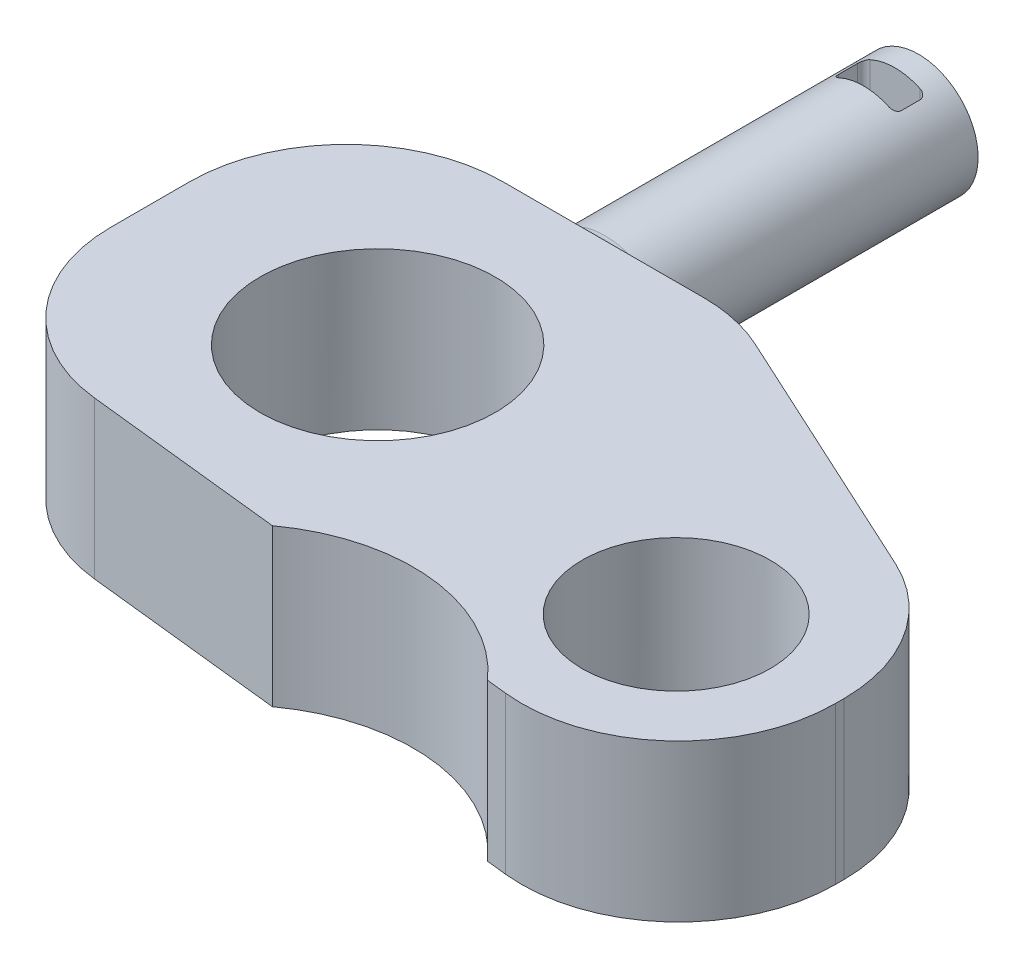
SolidWorks part; units mm, degrees
ref_plane "Front" through (0, 0, 0) normal (0, 0, 1) x (1, 0, 0)
ref_plane "Top" through (0, 0, 0) normal (0, 1, 0) x (1, 0, 0)
ref_plane "Right" through (0, 0, 0) normal (1, 0, 0) x (0, 0, -1)
sketch "Sketch1" plane through (0, 0, 0) normal (0, 0, 1) x (1, 0, 0)
  circle A0 centre (0, 0) radius 5
  dimension "D1" = 10
extrude "Boss-Extrude1" add sketch "Sketch1" along normal blind 20
sketch "Sketch2" plane through (0, 0, 0) normal (0, 0, -1) x (-1, 0, 0)
  circle A0 centre (0, 0) radius 3.98
  circle A1 centre (0, 0) radius 5 construction
  circle A2 centre (0, 0) radius 5
  dimension "D1" = 7.96
extrude "Cut-Extrude2" cut sketch "Sketch2" against normal blind 8 contours A0 | A2
sketch "Sketch8" plane through (0, 0, 20) normal (0, 0, 1) x (1, 0, 0)
  circle A0 centre (0, 0) radius 5
  dimension "D1" = 10
extrude "Boss-Extrude2" add sketch "Sketch8" along normal blind 20
sketch "Sketch9" plane through (0, 0, 40) normal (0, 0, 1) x (1, 0, 0)
  line L1 (0, 5) -> (35, 5)
  line L3 (0, -5) -> (35, -5)
  line L4 (35, 5) -> (35, -5)
  circle A1 centre (0, 0) radius 5 construction
  arc A2 (0, -5) -> (0, 5) centre (0, 0) ccw
  dimension "D1" = 35
  dimension "D2" = 5
  dimension "D3" = 10
extrude "Boss-Extrude3" add sketch "Sketch9" against normal blind 31.5
sketch "Sketch10" plane through (0, 0, 40) normal (0, 0, 1) x (1, 0, 0)
  line L5 (0, 5) -> (-15, 5)
  line L7 (0, -5) -> (-15, -5)
  line L8 (-15, 5) -> (-15, -5)
  arc A0 (0, 5) -> (0, -5) centre (0, 0) ccw construction
  arc A1 (0, 5) -> (0, -5) centre (0, 0) ccw
  dimension "D1" = 15
extrude "Boss-Extrude4" add sketch "Sketch10" against normal blind 31.5
sketch "Sketch12" plane through (0, 5, 0) normal (0, 1, 0) x (1, 0, 0)
  line L0 (0, -8.5) -> (-15, -8.5) construction
  line L3 (0, -21.5) -> (73.8631, -37.7534) construction
  line L4 (0, -21.5) -> (73.9968, -21.5) construction
  circle A0 centre (0, -21.5) radius 7.5
  circle A3 centre (24.4159, -26.8726) radius 6
  dimension "D1" = 15
  dimension "D3" = 12.41
  dimension "D4" = 12
  dimension "D2" = 13
  dimension "D5" = 25
extrude "Cut-Extrude3" cut sketch "Sketch12" against normal blind 31.5
sketch "Sketch14" plane through (0, 5, 0) normal (0, 1, 0) x (1, 0, 0)
  line L1 (35, -8.5) -> (0, -8.5) construction
  line L2 (35, -8.5) -> (35, -40) construction
  line L4 (-15, -8.5) -> (-15, -40) construction
  line L6 (-15, -40) -> (35, -40)
  line L7 (35, -40) -> (35, -37.3683)
  line L8 (34.4159, -37.8726) -> (-15, -32.5)
  line L9 (-15, -32.5) -> (-15, -40)
  line L10 (34.4159, -19.7562) -> (34.4159, -37.8726)
  line L11 (-15, -40) -> (35, -40)
  line L12 (35, -40) -> (35, -8.5)
  line L13 (35, -8.5) -> (0, -8.5)
  line L14 (0, -8.5) -> (-15, -8.5)
  line L15 (-15, -8.5) -> (-15, -40)
  line L18 (35, -8.5) -> (10, -8.5)
  line L22 (35, -37.3683) -> (35, -8.5)
  line L23 (10, -8.5) -> (34.4159, -19.7562)
  circle A0 centre (0, -21.5) radius 7.5 construction
  dimension "D2" = 10
  dimension "D3" = 11
  dimension "D4" = 7.1164
  dimension "D6" = 10
  dimension "D7" = 11
  dimension "D1" = 0
extrude "Cut-Extrude4" cut sketch "Sketch14" against normal through all
fillet "Fillet1" radius 10 5 edges at (-15, 0, 8.5) (-15, 0, 32.5) (34.4159, 0, 37.8726) (34.4159, 0, 19.7562) (10, 0, 8.5)
sketch "Sketch15" plane through (0, 5, 0) normal (0, 1, 0) x (1, 0, 0)
  line L0 (0, -21.5) -> (57.2418, -34.0932)
  line L1 (0, -21.5) -> (51.5086, -21.5)
  dimension "D1" = 12.407
sketch "Sketch17" plane through (0, 0, 0) normal (0, 0, -1) x (-1, 0, 0)
  circle A1 centre (0, 0) radius 3.98
  circle A2 centre (0, 0) radius 3.98
  dimension "D1" = 0
extrude "Boss-Extrude5" add sketch "Sketch17" along normal blind 13
sketch "Sketch18" plane through (0, 5, 0) normal (0, 1, 0) x (1, 0, 0)
  line L0 (-3.98, 8) -> (3.98, 8) construction
  line L1 (-3.98, 13) -> (-3.98, -8) construction
  line L2 (3.98, -8) -> (3.98, 13) construction
  line L3 (3.98, 13) -> (-3.98, 13) construction
  line L4 (0, 8) -> (0, 13) construction
  line L5 (-1.6, 11.5) -> (1.6, 11.5)
  line L6 (-2, 11.1) -> (-2, 9.9)
  line L7 (-1.6, 9.5) -> (1.6, 9.5)
  line L8 (2, 11.1) -> (2, 9.9)
  line L9 (-2, 10.5) -> (2, 10.5) construction
  arc A0 (1.6, 11.5) -> (2, 11.1) centre (1.6, 11.1) cw
  arc A1 (1.6, 9.5) -> (2, 9.9) centre (1.6, 9.9) ccw
  arc A2 (-2, 9.9) -> (-1.6, 9.5) centre (-1.6, 9.9) ccw
  arc A3 (-1.6, 11.5) -> (-2, 11.1) centre (-1.6, 11.1) ccw
  point P14 (0, 10.5)
  point P17 (0, 10.5)
  point P22 (2, 11.5)
  point P25 (2, 9.5)
  point P30 (-2, 11.5)
  dimension "D4" = 0.4
  dimension "D1" = 5
  dimension "D2" = 2
  dimension "D3" = 4
extrude "Cut-Extrude5" cut sketch "Sketch18" against normal through all
sketch "Sketch19" plane through (0, 0, 8) normal (0, 0, -1) x (-1, 0, 0)
  circle A0 centre (0, 0) radius 5 construction
  circle A1 centre (0, 0) radius 3.98
  circle A2 centre (0, 0) radius 3.98
  circle A3 centre (0, 0) radius 5
  dimension "D1" = 0
extrude "Cut-Extrude6" cut sketch "Sketch19" against normal up to surface (0.5 mm away) up to face at (5.1529, 0, 8.5)
sketch "Sketch20" plane through (0, 0, -13) normal (0, 0, -1) x (-1, 0, 0)
  circle A0 centre (0, 0) radius 3.8
  circle A1 centre (0, 0) radius 3.98 construction
  circle A2 centre (0, 0) radius 3.98
  dimension "D1" = 7.6
extrude "Cut-Extrude7" cut sketch "Sketch20" against normal up to surface (21.5 mm away) up to face at (1.4029, 0, 8.5)
fillet "Fillet2" radius 1.5 1 edges at (3.8, 0, 8.5)
sketch "Sketch21" plane through (0, -5, 0) normal (0, -1, 0) x (1, 0, 0)
  line L0 (-6.0809, 33.4697) -> (23.335, 36.6679)
  line L1 (23.335, 36.6679) -> (-6.0809, 33.4697) construction
  arc A1 (6.6373, 34.8525) -> (22.0385, 36.5269) centre (13.4191, 44.1399) ccw
  point P7 (22.2808, 36.5533)
  point P10 (13.4191, 43.6671)
  dimension "D2" = 11.5
  dimension "D1" = 19.5
  dimension "D3" = 8.5
extrude "Cut-Extrude9" cut sketch "Sketch21" against normal blind 10 contours L0 A1
